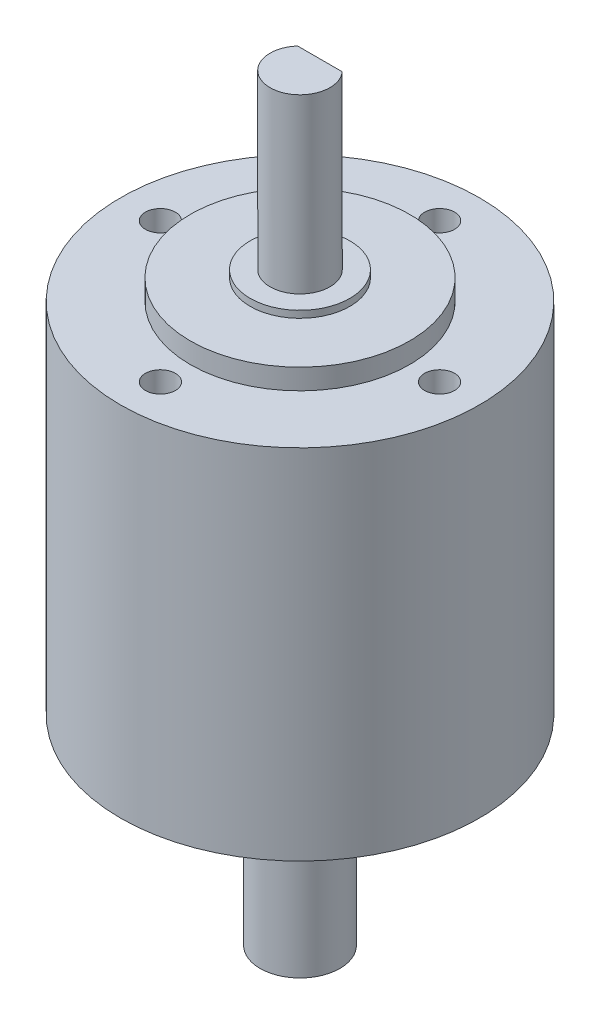
SolidWorks part; units mm, degrees
ref_plane "Front Plane" through (0, 0, 0) normal (0, 0, 1) x (1, 0, 0)
ref_plane "Top Plane" through (0, 0, 0) normal (0, 1, 0) x (1, 0, 0)
ref_plane "Right Plane" through (0, 0, 0) normal (1, 0, 0) x (0, 0, -1)
sketch "Sketch1" plane through (0, 0, 0) normal (0, 1, 0) x (1, 0, 0)
  circle A0 centre (0, 0) radius 18
  dimension "D1" = 36
extrude "Boss-Extrude1" add sketch "Sketch1" along normal mid plane 35.8902
sketch "Sketch2" plane through (0, 17.9451, 0) normal (0, 1, 0) x (1, 0, 0)
  circle A0 centre (0, 0) radius 11
  dimension "D1" = 22
extrude "Boss-Extrude2" add sketch "Sketch2" along normal mid plane 40.005 from surface starting at plane "Top Plane"
sketch "Sketch3" plane through (0, 20.0025, 0) normal (0, 1, 0) x (1, 0, 0)
  circle A0 centre (0, 0) radius 3
  dimension "D1" = 6
extrude "Boss-Extrude4" add sketch "Sketch3" along normal blind 18
sketch "Sketch4" plane through (0, 38.0025, 0) normal (0, 1, 0) x (1, 0, 0)
  line L0 (-2.2361, 2) -> (2.2361, 2)
  line L1 (0, -3) -> (0, 2) construction
  arc A0 (0, -3) -> (2.2361, 2) centre (0, 0) ccw construction
  circle A1 centre (0, 0) radius 3
  arc A2 (2.2361, 2) -> (-2.2361, 2) centre (0, 0) ccw
  arc A3 (-2.2361, 2) -> (0, -3) centre (0, 0) ccw construction
  dimension "D2" = 5
  dimension "D1" = 0
extrude "Cut-Extrude1" cut sketch "Sketch4" against normal blind 15
sketch "Sketch5" plane through (0, 17.9451, 0) normal (0, 1, 0) x (1, 0, 0)
  circle A0 centre (0, 0) radius 14 construction
  circle A1 centre (0, 14) radius 1.5
  circle A2 centre (-14, 0) radius 1.5
  circle A3 centre (0, -14) radius 1.5
  circle A4 centre (14, 0) radius 1.5
  dimension "D1" = 28
  dimension "D2" = 3
extrude "Cut-Extrude2" cut sketch "Sketch5" against normal blind 4
mirror "Mirror1" about plane through (0, 0, 0) normal (0, 1, 0) of "Cut-Extrude2", "Cut-Extrude1"
sketch "Sketch6" plane through (0, -20.0025, 0) normal (0, -1, 0) x (1, 0, 0)
  circle A0 centre (0, 0) radius 4
  dimension "D1" = 8
extrude "Boss-Extrude5" add sketch "Sketch6" along normal blind 18
sketch "Sketch7" plane through (0, -38.0025, 0) normal (0, -1, 0) x (1, 0, 0)
  line L0 (-2.6458, -3) -> (2.6458, -3)
  line L1 (0, -3) -> (0, -4) construction
  arc A0 (2.6458, -3) -> (-2.6458, -3) centre (0, 0) cw
  circle A2 centre (0, 0) radius 4 construction
  dimension "D1" = 1
extrude "Cut-Extrude3" cut sketch "Sketch7" against normal offset from surface (15 mm away) 3 up to face at (0, -20.0025, -4)
sketch "Sketch9" plane through (0, 0, 0) normal (0, 1, 0) x (1, 0, 0)
  circle A0 centre (0, 0) radius 5
  dimension "D1" = 10
extrude "Boss-Extrude6" add sketch "Sketch9" along normal mid plane 41.402
